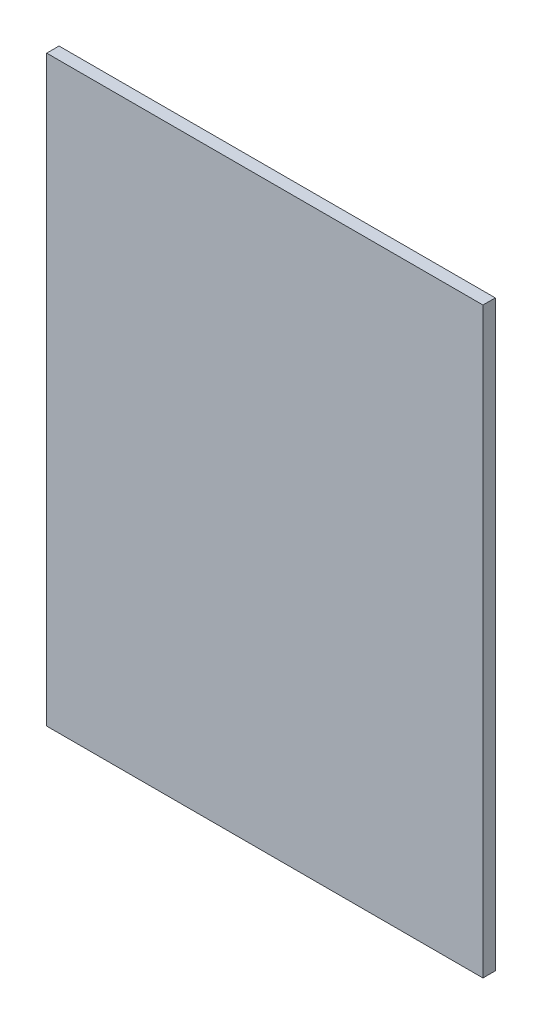
SolidWorks part; units mm, degrees
ref_plane "Front Plane" through (0, 0, 0) normal (0, 0, 1) x (1, 0, 0)
ref_plane "Top Plane" through (0, 0, 0) normal (0, 1, 0) x (1, 0, 0)
ref_plane "Right Plane" through (0, 0, 0) normal (1, 0, 0) x (0, 0, -1)
sketch "Sketch1" plane through (0, 0, 0) normal (0, 0, 1) x (1, 0, 0)
  line L1 (-90.5335, 103.6022) -> (134.0132, 103.6022)
  line L2 (-90.5335, 103.6022) -> (-90.5335, -196.3978)
  line L3 (-90.5335, -196.3978) -> (134.0132, -196.3978)
  line L4 (134.0132, 103.6022) -> (134.0132, -196.3978)
  dimension "D1" = 300
extrude "Boss-Extrude1" add sketch "Sketch1" along normal blind 6.35
sketch "Sketch2" plane through (0, 0, 0) normal (0, 0, -1) x (-1, 0, 0)
  line L0 (-21.7398, -196.3978) -> (-21.7398, 103.6022) construction
  line L1 (90.5335, -196.3978) -> (-134.0132, -196.3978) construction
  line L2 (-134.0132, 103.6022) -> (90.5335, 103.6022) construction
  line L3 (-36.7398, 4.5453) -> (-6.7398, 4.5453) construction
  line L4 (-36.7398, 94.4025) -> (-6.7398, 94.4025) construction
  point P8 (-21.7398, 4.5453)
  point P11 (-21.7398, 94.4025)
  dimension "D1" = 30
  dimension "D2" = 30
